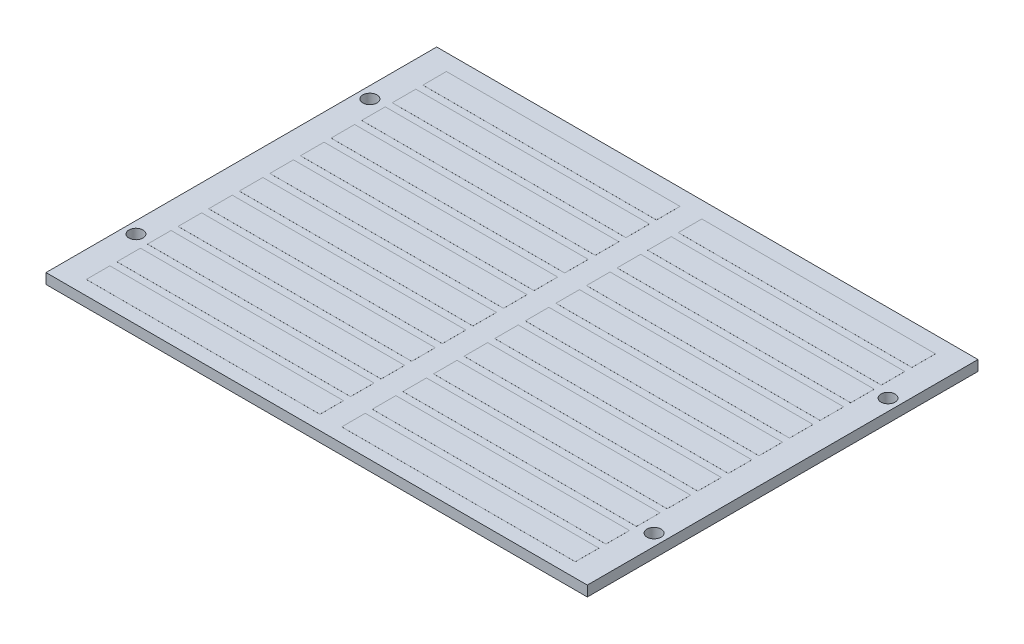
SolidWorks part; units mm, degrees
ref_plane "Спереди" through (0, 0, 0) normal (0, 0, 1) x (1, 0, 0)
ref_plane "Сверху" through (0, 0, 0) normal (0, 1, 0) x (1, 0, 0)
ref_plane "Справа" through (0, 0, 0) normal (1, 0, 0) x (0, 0, -1)
sketch "Эскиз1" plane through (0, 0, 0) normal (0, 1, 0) x (1, 0, 0)
  line L1 (-57.5, -41.5) -> (57.5, -41.5)
  line L2 (-57.5, -41.5) -> (-57.5, 41.5)
  line L3 (-57.5, 41.5) -> (57.5, 41.5)
  line L4 (57.5, -41.5) -> (57.5, 41.5)
  line L5 (-57.5, -41.5) -> (57.5, 41.5) construction
  line L6 (-57.5, 41.5) -> (57.5, -41.5) construction
  point P0 (0, 0)
  dimension "D1" = 83
  dimension "D2" = 115
extrude "Бобышка-Вытянуть1" add sketch "Эскиз1" along normal blind 2.2
sketch "Эскиз2" plane through (0, 2.2, 0) normal (0, 1, 0) x (1, 0, 0)
  line L0 (-57.5, 0) -> (57.5, 0) construction
  line L1 (2.3165, -38.4883) -> (51.945, -38.4883)
  line L2 (2.3165, -38.4883) -> (2.3165, -33.4883)
  line L3 (2.3165, -33.4883) -> (51.945, -33.4883)
  line L4 (51.945, -38.4883) -> (51.945, -33.4883)
  line L5 (2.3165, -38.4883) -> (51.945, -33.4883) construction
  line L6 (2.3165, -33.4883) -> (51.945, -38.4883) construction
  line L7 (-57.5, 41.5) -> (-57.5, -41.5) construction
  line L8 (57.5, -41.5) -> (57.5, 41.5) construction
  line L9 (0, -41.5) -> (0, 41.5) construction
  line L10 (-57.5, -41.5) -> (57.5, -41.5) construction
  line L11 (57.5, 41.5) -> (-57.5, 41.5) construction
  point P0 (27.1307, -35.9883)
  dimension "D1" = 5
extrude "Бобышка-Вытянуть2" add sketch "Эскиз2" along normal blind 0.01
pattern_linear "Линейный массив1" count 12 spacing 6.5 along (0, 0, -1) of "Бобышка-Вытянуть2"
mirror "Зеркальное отражение1" about plane through (0, 0, 0) normal (1, 0, 0) of "Линейный массив1"
sketch "Эскиз3" plane through (0, 2.2, 0) normal (0, 1, 0) x (1, 0, 0)
  circle A0 centre (55.0333, 24.8496) radius 1.5
extrude "Вырез-Вытянуть1" cut sketch "Эскиз3" against normal blind 10
ref_plane "Плоскость1" through (0, 0, 0) normal (0, 0, -1) x (-1, 0, 0)
ref_plane "Плоскость2" through (0, 0, 0) normal (1, 0, 0) x (0, 0, -1)
mirror "Зеркальное отражение2" about plane through (0, 0, 0) normal (0, 0, -1) of "Вырез-Вытянуть1"
mirror "Зеркальное отражение3" about plane through (0, 0, 0) normal (1, 0, 0) of "Зеркальное отражение2", "Вырез-Вытянуть1"
